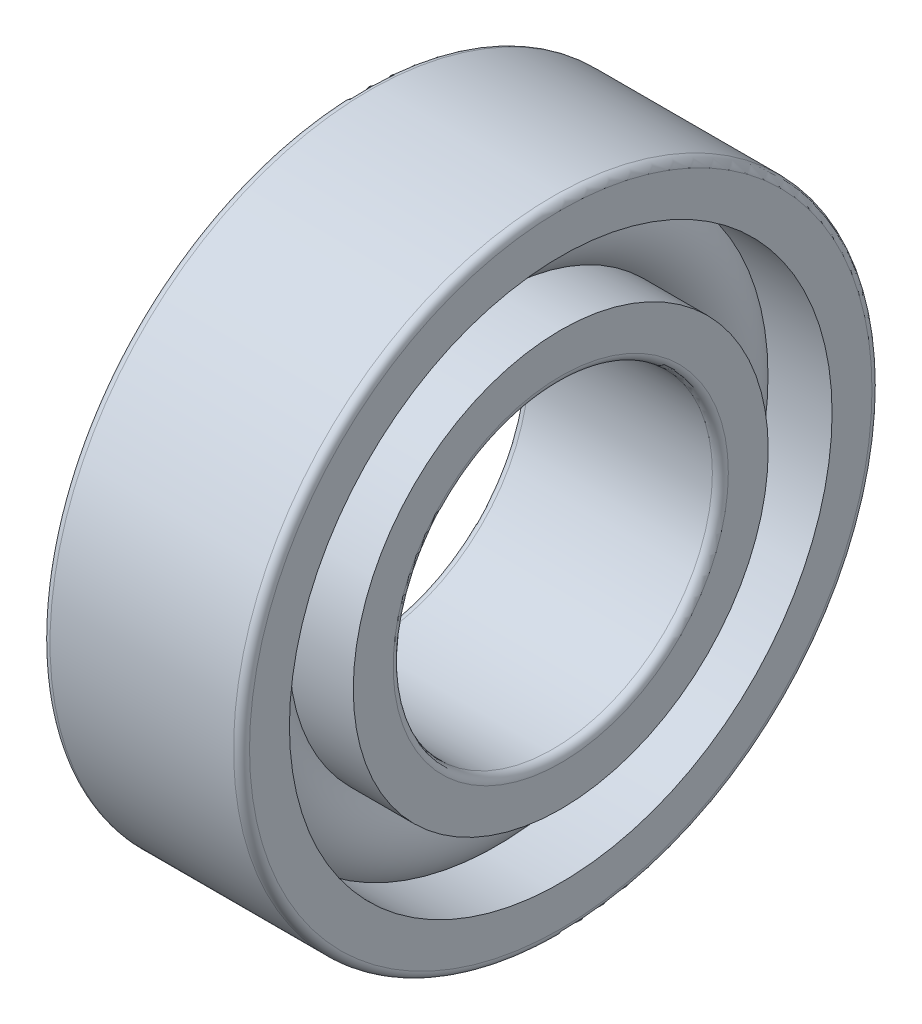
SolidWorks part; units mm, degrees
ref_plane "Plane1" through (0, 0, 0) normal (0, 0, 1) x (1, 0, 0)
ref_plane "Plane2" through (0, 0, 0) normal (0, 1, 0) x (1, 0, 0)
ref_plane "Plane3" through (0, 0, 0) normal (1, 0, 0) x (0, 0, -1)
other "Configuration Table"
sketch "Clipboard" plane through (0, 0, 0) normal (0, 0, 1) x (1, 0, 0)
  line L0 (-10, 0) -> (10, 0) construction
  line L1 (0, 0) -> (22.3471, -0.7804)
  line L2 (0, 0) -> (5.9963, 0.2094)
  line L3 (0, 0) -> (22.3471, -0.7804)
  line L4 (0, 0) -> (-22.3573, -0.3902)
  dimension "BallCLRad" = 6
sketch "CagSpiSke" plane through (0, 0, 0) normal (0, 0, 1) x (1, 0, 0)
  line L0 (0.12, 5.8) -> (0.12, 6.2)
  line L1 (0.12, 6.2) -> (-0.12, 6.2)
  line L2 (-0.12, 6.2) -> (-0.12, 5.8)
  line L3 (-0.12, 5.8) -> (0.12, 5.8)
  line L4 (-20.6375, 0) -> (20.6375, 0) construction
  line L5 (0, 0) -> (0, 23.7692) construction
  dimension "OD" = 12.4
  dimension "ID" = 11.6
revolve "CageSpine" add sketch "CagSpiSke" angle 0.001 about L4 reverse direction yes
ref_axis "Axis1" through (-50, 0, 0) along (1, 0, 0)
sketch "CagBalSke" plane through (0, 0, 0) normal (0, 0, 1) x (1, 0, 0)
  line L0 (-1.32, 6) -> (1.32, 6)
  line L1 (-1.905, 6) -> (1.905, 6) construction
  line L2 (-10, 0) -> (10, 0) construction
  line L3 (0, 0) -> (0, 24) construction
  arc A0 (1.32, 6) -> (-1.32, 6) centre (0, 6) cw
  dimension "BallCLRad" = 6
revolve "CageBall" [suppressed] add sketch "CagBalSke" angle 360 about L1 reverse direction yes
pattern_circular "CageBalls" [suppressed] count 2 every 180 about axis through (-50, 0, 0) along (1, 0, 0)
sketch "CagTrmODSke" plane through (0, 0, 0) normal (0, 0, 1) x (1, 0, 0)
  line L0 (1.321, 6.2) -> (1.321, 7.321)
  line L1 (1.321, 7.321) -> (-1.321, 7.321)
  line L2 (-1.321, 7.321) -> (-1.321, 6.2)
  line L3 (-1.321, 6.2) -> (1.321, 6.2)
  line L4 (-20.6375, 0) -> (20.6375, 0) construction
  line L5 (0, 0) -> (0, 25) construction
  dimension "Width" = 2.642
  dimension "ID" = 12.4
  dimension "OD" = 14.642
revolve "CageTrimOD" [suppressed] cut sketch "CagTrmODSke" angle 360 about L4 reverse direction yes
sketch "CagTrmIDSke" plane through (0, 0, 0) normal (0, 0, 1) x (1, 0, 0)
  line L0 (1.321, 4.681) -> (1.321, 5.8)
  line L1 (1.321, 5.8) -> (-1.321, 5.8)
  line L2 (-1.321, 5.8) -> (-1.321, 4.681)
  line L3 (-1.321, 4.681) -> (1.321, 4.681)
  line L4 (-20.6375, 0) -> (20.6375, 0) construction
  line L5 (0, 0) -> (0, 25) construction
  dimension "Width" = 2.642
  dimension "ID" = 9.362
  dimension "OD" = 11.6
revolve "CageTrimID" [suppressed] cut sketch "CagTrmIDSke" angle 360 about L4 reverse direction yes
sketch "BalSimSke" plane through (0, 0, 0) normal (0, 0, 1) x (1, 0, 0)
  line L0 (-10, 0) -> (10, 0) construction
  line L1 (-10, 6) -> (10, 6) construction
  line L2 (0, 0) -> (0, 23) construction
  circle A0 centre (0, 6) radius 1.2
  dimension "BallCLRad" = 6
  dimension "Ball_diameter" = 2.4
revolve "BallsSimplified" add sketch "BalSimSke" angle 360 about L0
sketch "BalDetSke" plane through (0, 0, 0) normal (0, 0, 1) x (1, 0, 0)
  line L0 (-1.2, 6) -> (1.2, 6)
  line L1 (-1.905, 6) -> (1.905, 6) construction
  line L2 (0, 0) -> (0, 25) construction
  arc A0 (1.2, 6) -> (-1.2, 6) centre (0, 6) cw
  dimension "BallCLRad" = 6
  dimension "Ball_diameter" = 2.4
revolve "BallDetailed" [suppressed] add sketch "BalDetSke" angle 360 about L1 reverse direction yes
sketch "InnRacSke" plane through (0, 0, 0) normal (0, 0, 1) x (1, 0, 0)
  line L0 (-0.8606, 5.2) -> (-2.5, 5.2)
  line L1 (-2.5, 5.2) -> (-2.5, 4.2)
  line L2 (-2.3, 4) -> (2.3, 4)
  line L3 (2.5, 4.2) -> (2.5, 5.2)
  line L4 (2.5, 5.2) -> (0.8606, 5.2)
  line L5 (-20.6375, 0) -> (20.6375, 0) construction
  line L6 (0, 0) -> (0, 30) construction
  arc A0 (-2.5, 4.2) -> (-2.3, 4) centre (-2.3, 4.2) ccw
  arc A1 (2.3, 4) -> (2.5, 4.2) centre (2.3, 4.2) ccw
  arc A2 (0.8606, 5.2) -> (-0.8606, 5.2) centre (0, 6) cw
  dimension "BallCLRad" = 6
  dimension "Fillet_radius" = 0.2
  dimension "Ball_diameter" = 2.35
  dimension "ID" = 8
  dimension "OD" = 10.4
  dimension "Width" = 5
revolve "InnerRace" add sketch "InnRacSke" angle 360 about L5 reverse direction yes
sketch "OutRacSke" plane through (0, 0, 0) normal (0, 0, 1) x (1, 0, 0)
  line L0 (-0.8606, 6.8) -> (-2.5, 6.8)
  line L1 (-2.5, 6.8) -> (-2.5, 7.8)
  line L2 (-2.3, 8) -> (2.3, 8)
  line L3 (2.5, 7.8) -> (2.5, 6.8)
  line L4 (2.5, 6.8) -> (0.8606, 6.8)
  line L5 (-20.6375, 0) -> (20.6375, 0) construction
  line L6 (0, 0) -> (0, 30) construction
  arc A0 (-2.5, 7.8) -> (-2.3, 8) centre (-2.3, 7.8) cw
  arc A1 (2.3, 8) -> (2.5, 7.8) centre (2.3, 7.8) cw
  arc A2 (0.8606, 6.8) -> (-0.8606, 6.8) centre (0, 6) ccw
  dimension "BallCLRad" = 6
  dimension "Fillet_radius" = 0.2
  dimension "Ball_diameter" = 2.35
  dimension "Width" = 5
revolve "OuterRace" add sketch "OutRacSke" angle 360 about L5 reverse direction yes
pattern_circular "BallsDetailed" [suppressed] count 2 every 180 about axis through (-50, 0, 0) along (1, 0, 0)
equation "\"BallCLRad@Clipboard\" = ( \"OD@OutRacSke\" + \"ID@InnRacSke\" ) / 4"
equation "\"BallCLRad@BalSimSke\" = \"BallCLRad@Clipboard\""
equation "\"BallCLRad@BalDetSke\" = \"BallCLRad@Clipboard\""
equation "\"BallCLRad@InnRacSke\" = \"BallCLRad@Clipboard\""
equation "\"BallCLRad@OutRacSke\" = \"BallCLRad@Clipboard\""
equation "\"Ball_diameter@InnRacSke\" = \"Ball_diameter@BalDetSke\" - 0.05"
equation "\"Ball_diameter@OutRacSke\" = \"Ball_diameter@BalDetSke\" - 0.05"
equation "\"Ball_diameter@BalSimSke\" = \"Ball_diameter@BalDetSke\""
equation "\"Width@OutRacSke\" = \"Width@InnRacSke\""
equation "\"Fillet_radius@OutRacSke\" = \"Fillet_radius@InnRacSke\""
equation "\"Max_count@Clipboard\" = int( 3.14159265 / atn(( \"Ball_diameter@BalDetSke\" / 2) / sqr( \"BallCLRad@Clipboard\"  *  \"BallCLRad@Clipboard\" - ( \"Ball_diameter@BalDetSke\" / 2) *  ( \"Ball_diameter@BalDetSke\" / 2))))"
equation "\"Max_count@Clipboard\" = ((sgn( \"Max_count@Clipboard\" - \"Count@Clipboard\" )-1)*( \"Max_count@Clipboard\" - \"Count@Clipboard\" ))/-2+ \"Count@Clipboard\""
equation "\"Count@BallsDetailed\" = int( \"Show_count@Clipboard\" ) "
equation "\"Count@BallsDetailed\" = ((sgn( \"Count@BallsDetailed\" - \"Max_count@Clipboard\" )-1)*( \"Count@BallsDetailed\" - \"Max_count@Clipboard\" ))/-2+ \"Max_count@Clipboard\""
equation "\"Count@BallsDetailed\" = ((sgn( \"Count@BallsDetailed\" - \"Min_count@Clipboard\" )+1)*( \"Count@BallsDetailed\" - \"Min_count@Clipboard\"))/2 +\"Min_count@Clipboard\""
equation "\"Angle@BallsDetailed\" = 360.0 / \"Max_count@Clipboard\""
equation "\"BallCLRad@CagBalSke\" = \"BallCLRad@Clipboard\""
equation "\"Count@CageBalls\" = \"Count@BallsDetailed\""
equation "\"Angle@CageBalls\" = \"Angle@BallsDetailed\""
equation "\"Angle@CageSpine\" =  \"Angle@CageBalls\" * ( \"Count@CageBalls\" -1 + int( \"Count@CageBalls\" / \"Max_count@Clipboard\" ) )  + 0.001 -  int( \"Count@CageBalls\" / \"Max_count@Clipboard\" ) * 0.001"
equation "\"Angle@CageSpine\" =  \"Angle@CageSpine\" * int( \"Min_count@Clipboard\" / 2) + int(1 / \"Min_count@Clipboard\")  * 0.001"
equation "\"CageWallOD@CagBalSke\" =  \"Ball_diameter@BalDetSke\" * 1.1"
equation "\"Thickness@CagSpiSke\" =  \"Ball_diameter@BalDetSke\" * 0.1"
equation "\"OD@CagTrmODSke\" = \"BallCLRad@Clipboard\" * 2 + \"CageWallOD@CagBalSke\" + 0.002"
equation "\"ID@CagTrmODSke\" = \"BallCLRad@Clipboard\" * 2 + \"Ball_diameter@BalDetSke\" / 6"
equation "\"OD@CagTrmIDSke\" = \"BallCLRad@Clipboard\" * 2 - \"Ball_diameter@BalDetSke\" / 6"
equation "\"ID@CagTrmIDSke\" = \"BallCLRad@Clipboard\" * 2 - \"CageWallOD@CagBalSke\" + 0.002"
equation "\"OD@CagSpiSke\" = \"ID@CagTrmODSke\""
equation "\"ID@CagSpiSke\" = \"OD@CagTrmIDSke\""
equation "\"Width@CagTrmODSke\" = \"CageWallOD@CagBalSke\" + 0.002"
equation "\"Width@CagTrmIDSke\" = \"CageWallOD@CagBalSke\" + 0.002"
